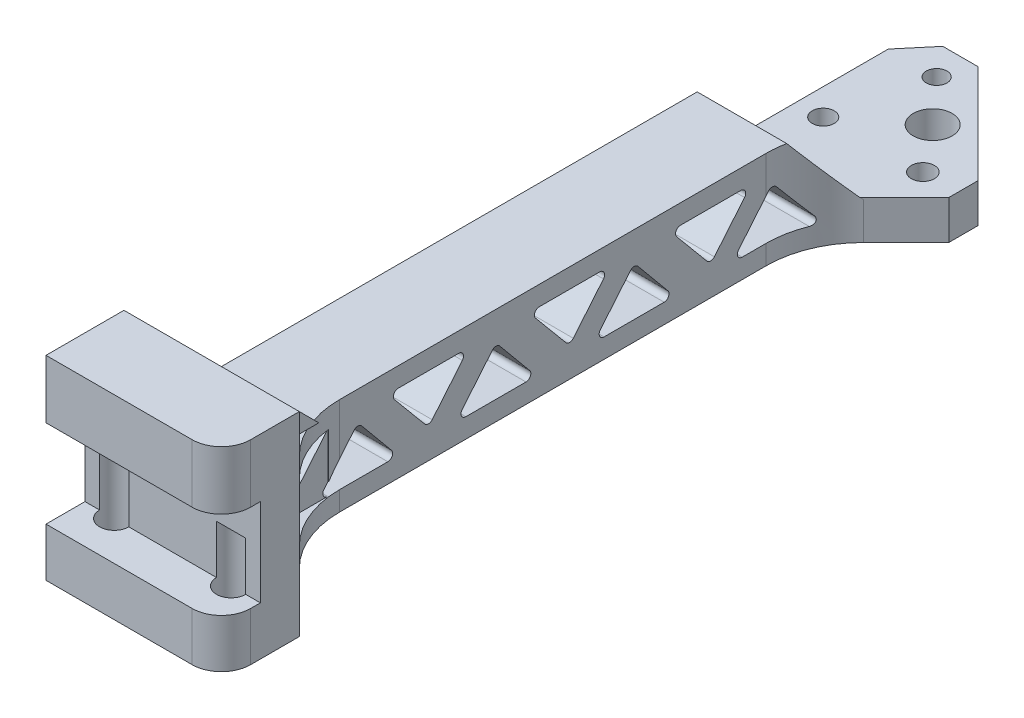
SolidWorks part; units mm, degrees
ref_plane "Front Plane" through (0, 0, 0) normal (0, 0, 1) x (1, 0, 0)
ref_plane "Top Plane" through (0, 0, 0) normal (0, 1, 0) x (1, 0, 0)
ref_plane "Right Plane" through (0, 0, 0) normal (1, 0, 0) x (0, 0, -1)
sketch "Sketch1" plane through (0, 0, 0) normal (0, 1, 0) x (1, 0, 0)
  line L0 (0, 0) -> (0, 86.44)
  line L1 (0, 0) -> (15, 0)
  line L2 (18, 3) -> (18, 8)
  line L3 (18, 8) -> (11.9289, 14.0711)
  line L4 (9, 21.1421) -> (9, 69.0482)
  line L5 (18, 8) -> (9.3573, 8) construction
  line L6 (0, 86.44) -> (2.5581, 89.482)
  line L7 (2.5581, 89.482) -> (6.1681, 89.482)
  line L8 (6.1681, 89.482) -> (16.3009, 79.3492)
  line L9 (16.3009, 79.3492) -> (16.3009, 76.3492)
  line L10 (16.3009, 76.3492) -> (9, 69.0482)
  line L11 (9, 82) -> (2.7119, 77.0543) construction
  line L12 (9, 82) -> (12.7093, 77.2839) construction
  arc A0 (15, 0) -> (18, 3) centre (15, 3) ccw
  arc A1 (9, 21.1421) -> (11.9289, 14.0711) centre (19, 21.1421) ccw
  circle A2 centre (15, 4) radius 1.5
  circle A3 centre (3, 4) radius 1.5
  circle A4 centre (9, 82) radius 2
  circle A5 centre (9, 82) radius 6 construction
  circle A6 centre (9, 82) radius 8 construction
  circle A7 centre (4.9644, 86.44) radius 1.0627
  circle A8 centre (2.7119, 77.0543) radius 1.1294
  circle A9 centre (12.7093, 77.2839) radius 1.1853
  point P9 (18, 0)
  dimension "D5" = 3
  dimension "D6" = 10
  dimension "D9" = 3
  dimension "D13" = 4
  dimension "D14" = 12
  dimension "D15" = 16
  dimension "D19" = 2.1254
  dimension "D1" = 86.44
  dimension "D2" = 82
  dimension "D3" = 18
  dimension "D4" = 8
  dimension "D7" = 9
  dimension "D8" = 45
  dimension "D10" = 4
  dimension "D11" = 3
  dimension "D12" = 12
  dimension "D16" = 3.61
  dimension "D17" = 14.33
  dimension "D18" = 3
  dimension "D20" = 3.042
  dimension "D21" = 4
  dimension "D22" = 90
extrude "Boss-Extrude1" add sketch "Sketch1" along normal blind 10
sketch "Sketch2" plane through (0, 0, 0) normal (-1, 0, 0) x (0, 0, 1)
  line L0 (-89.482, 5) -> (0, 5) construction
  line L1 (-89.482, 10) -> (-89.482, 0) construction
  line L2 (0, 10) -> (0, 0) construction
  line L3 (-89.482, 7) -> (0, 7) construction
  line L4 (-89.482, 8) -> (0, 8) construction
  line L5 (-86.44, 10) -> (0, 10) construction
  line L6 (-89.482, 2) -> (0, 2) construction
  line L7 (-89.482, 3) -> (0, 3) construction
  line L8 (-9, 8) -> (-9, 2)
  line L9 (-9, 2) -> (-14, 2)
  line L10 (-14, 2) -> (-9, 8)
  line L11 (-19.9367, 8) -> (-11.6034, 8)
  line L12 (-11.6034, 8) -> (-15.7701, 3)
  line L13 (-15.7701, 3) -> (-19.9367, 8)
  line L14 (-30.2501, 3) -> (-34.4167, 8)
  line L15 (-34.4167, 8) -> (-26.0834, 8)
  line L16 (-26.0834, 8) -> (-30.2501, 3)
  line L17 (-44.7301, 3) -> (-48.8967, 8)
  line L18 (-48.8967, 8) -> (-40.5634, 8)
  line L19 (-40.5634, 8) -> (-44.7301, 3)
  line L20 (-59.2101, 3) -> (-63.3767, 8)
  line L21 (-63.3767, 8) -> (-55.0434, 8)
  line L22 (-55.0434, 8) -> (-59.2101, 3)
  line L23 (-23.0085, 7) -> (-18.8419, 2)
  line L24 (-18.8419, 2) -> (-27.1419, 2)
  line L25 (-27.1419, 2) -> (-23.0085, 7)
  line L26 (-41.3219, 2) -> (-37.1885, 7)
  line L27 (-37.1885, 7) -> (-33.0219, 2)
  line L28 (-33.0219, 2) -> (-41.3219, 2)
  line L29 (-55.5019, 2) -> (-51.3685, 7)
  line L30 (-51.3685, 7) -> (-47.2019, 2)
  line L31 (-47.2019, 2) -> (-55.5019, 2)
  line L32 (-69.6819, 2) -> (-65.5485, 7)
  line L33 (-65.5485, 7) -> (-61.3819, 2)
  line L34 (-61.3819, 2) -> (-69.6819, 2)
  line L35 (-68.482, 8) -> (-73.482, 2)
  line L36 (-73.482, 2) -> (-73.482, 8)
  line L37 (-73.482, 8) -> (-68.482, 8)
  point P21 (-15.7701, 8)
  dimension "D1" = 2
  dimension "D2" = 1
  dimension "D3" = 9
  dimension "D4" = 5
  dimension "D5" = 8.3333
  dimension "D6" = 2
  dimension "D8" = 3
  dimension "D9" = 8.3
  dimension "D10" = 4
  dimension "D11" = 16
  dimension "D12" = 5
  dimension "D7" = 4
extrude "Cut-Extrude1" cut sketch "Sketch2" against normal through all
sketch "Sketch3" plane through (9, 0, 0) normal (1, 0, 0) x (0, 0, -1)
  line L0 (8, 10) -> (8, 0) construction
  line L1 (8, 8) -> (19.9367, 8)
  line L2 (8, 8) -> (8, 2)
  line L3 (8, 2) -> (19.9367, 2)
  line L4 (19.9367, 8) -> (19.9367, 2)
  line L5 (14.0711, 8) -> (19.9367, 8) construction
  line L6 (21.1421, 2) -> (18.8419, 2) construction
  point P6 (19.7016, 8)
  point P9 (19.9367, 8)
  point P11 (19.9367, 2)
extrude "Cut-Extrude2" cut sketch "Sketch3" along normal through all
fillet "Fillet3" radius 10 1 edges at (9, 5.0435, -69.0482)
fillet "Fillet33" radius 0.5 1 edges at (4.5, 8, -48.8967)
fillet "Fillet34" radius 0.5 1 edges at (4.5, 3, -59.2101)
fillet "Fillet35" radius 0.5 1 edges at (4.5, 2, -61.3819)
fillet "Fillet36" radius 0.5 1 edges at (4.5, 3, -30.2501)
fillet "Fillet37" radius 0.5 1 edges at (4.5, 7, -23.0085)
fillet "Fillet38" radius 0.5 1 edges at (4.5, 3, -44.7301)
fillet "Fillet39" radius 0.5 1 edges at (4.5, 7, -37.1885)
fillet "Fillet40" radius 0.5 1 edges at (4.5, 2, -41.3219)
fillet "Fillet41" radius 0.5 1 edges at (4.5, 2, -55.5019)
fillet "Fillet42" radius 0.5 1 edges at (4.5, 2, -47.2019)
fillet "Fillet43" radius 0.5 1 edges at (4.5, 2, -18.8419)
fillet "Fillet44" radius 0.5 1 edges at (6.7169, 8, -73.482)
fillet "Fillet45" radius 0.5 1 edges at (6.7169, 2, -73.482)
fillet "Fillet46" radius 0.5 1 edges at (4.5, 7, -51.3685)
fillet "Fillet47" radius 0.5 1 edges at (4.8306, 8, -68.482)
fillet "Fillet48" radius 0.5 1 edges at (4.5103, 7, -65.5485)
fillet "Fillet49" radius 0.5 1 edges at (5.1071, 2, -69.6819)
fillet "Fillet50" radius 0.5 1 edges at (4.5, 2, -27.1419)
fillet "Fillet51" radius 0.5 1 edges at (4.5, 3, -15.7701)
fillet "Fillet52" radius 0.5 1 edges at (4.5, 8, -55.0434)
fillet "Fillet53" radius 0.5 1 edges at (4.5, 8, -26.0834)
fillet "Fillet54" radius 0.5 1 edges at (4.5, 8, -63.3767)
fillet "Fillet55" radius 0.5 1 edges at (4.5, 8, -40.5634)
fillet "Fillet56" radius 0.5 1 edges at (4.5, 8, -34.4167)
fillet "Fillet57" radius 0.5 1 edges at (4.5, 2, -33.0219)
fillet "Fillet59" radius 0.3 1 edges at (4.5, 8, -11.6034)
sketch "Sketch4" plane through (0, 10, 0) normal (0, 1, 0) x (1, 0, 0)
  line L1 (0, 0) -> (15, 0)
  line L2 (0, 0) -> (0, 8)
  line L3 (0, 8) -> (18, 8)
  line L4 (18, 3) -> (18, 8)
  arc A0 (15, 0) -> (18, 3) centre (15, 3) ccw
  dimension "D1" = 3
extrude "Boss-Extrude2" add sketch "Sketch4" along normal blind 10
sketch "Sketch5" plane through (18, 0, 0) normal (1, 0, 0) x (0, 0, -1)
  line L0 (0, 20) -> (0, 0) construction
  line L1 (0, 14) -> (4, 14)
  line L2 (0, 14) -> (0, 5)
  line L3 (0, 5) -> (4, 5)
  line L4 (4, 14) -> (4, 5)
  line L5 (3, 20) -> (8, 20) construction
  line L6 (3, 0) -> (8, 0) construction
  dimension "D1" = 6
  dimension "D2" = 5
  dimension "D3" = 4
extrude "Cut-Extrude3" cut sketch "Sketch5" against normal through all
sketch "Sketch6" plane through (0, 0, 0) normal (-1, 0, 0) x (0, 0, 1)
  line L0 (-8, 20) -> (-18, 10)
  line L1 (-86.44, 10) -> (-8, 10) construction
  line L2 (-18, 10) -> (-8, 10)
  line L3 (-8, 10) -> (-8, 20)
  dimension "D1" = 45
extrude "Boss-Extrude3" add sketch "Sketch6" against normal blind 10
sketch "Sketch7" plane through (0, 0, 0) normal (-1, 0, 0) x (0, 0, 1)
  line L0 (-73.482, 7.5) -> (-73.482, 3.381) construction
  line L1 (-72.5979, 3.0609) -> (-69.1654, 7.1799) construction
  line L2 (-69.5495, 8) -> (-72.982, 8) construction
  line L3 (-73.482, 7.5) -> (-73.482, 3.381)
  line L4 (-72.5979, 3.0609) -> (-69.1654, 7.1799)
  line L5 (-69.5495, 8) -> (-72.982, 8)
  arc A0 (-72.982, 8) -> (-73.482, 7.5) centre (-72.982, 7.5) ccw construction
  arc A1 (-73.482, 3.381) -> (-72.5979, 3.0609) centre (-72.982, 3.381) ccw construction
  arc A2 (-69.1654, 7.1799) -> (-69.5495, 8) centre (-69.5495, 7.5) ccw construction
  arc A3 (-72.982, 8) -> (-73.482, 7.5) centre (-72.982, 7.5) ccw
  arc A4 (-73.482, 3.381) -> (-72.5979, 3.0609) centre (-72.982, 3.381) ccw
  arc A5 (-69.1654, 7.1799) -> (-69.5495, 8) centre (-69.5495, 7.5) ccw
extrude "Boss-Extrude4" add sketch "Sketch7" against normal up to surface (9.5013 mm away) up to face at (13.2884, 5.3541, -73.3367)
sketch "Sketch8" plane through (0, 0, 0) normal (1, 0, 0) x (0, 0, -1)
  line L0 (66.8311, 10) -> (71.7911, 4)
  line L1 (71.9772, 10) -> (64.9061, 10) construction
  line L2 (71.7911, 4) -> (89.482, 4)
  line L3 (89.482, 10) -> (89.482, 0) construction
  line L4 (89.482, 4) -> (89.482, 10)
  line L5 (89.482, 10) -> (66.8311, 10)
  line L6 (79.3492, 0) -> (89.482, 0) construction
  line L7 (65.9324, 6.5357) -> (69.0052, 2.8186) construction
  dimension "D1" = 4
  dimension "D2" = 2.9
extrude "Cut-Extrude6" cut sketch "Sketch8" along normal through all
